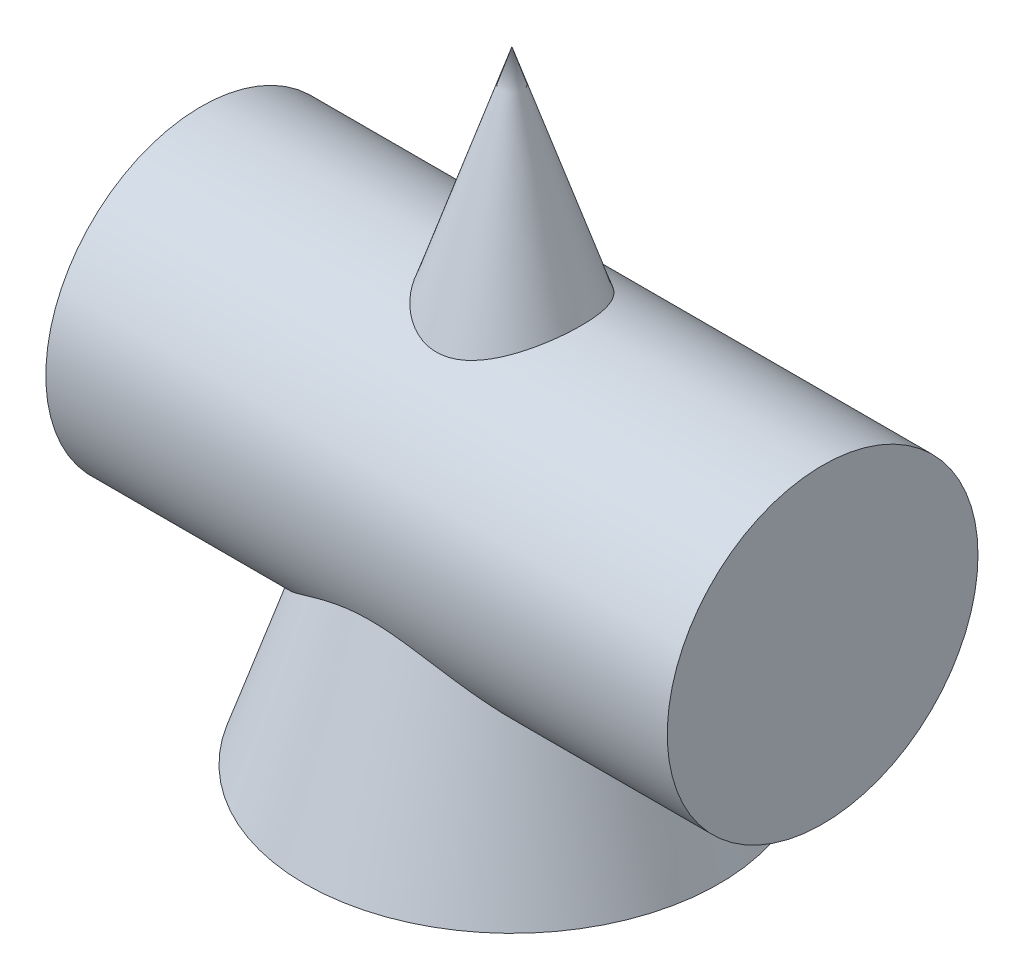
SolidWorks part; units mm, degrees
ref_plane "前视基准面" through (0, 0, 0) normal (0, 0, 1) x (1, 0, 0)
ref_plane "上视基准面" through (0, 0, 0) normal (0, 1, 0) x (1, 0, 0)
ref_plane "右视基准面" through (0, 0, 0) normal (1, 0, 0) x (0, 0, -1)
other "Configuration Table"
sketch "草图1" plane through (0, 0, 0) normal (0, 1, 0) x (1, 0, 0)
  circle A0 centre (0, 0) radius 20
sketch "草图3" plane through (0, 0, 0) normal (0, 0, 1) x (1, 0, 0)
  point P5 (0, 60)
loft "放样2" add profiles "草图1", "草图3"
sketch "草图4" plane through (0, 0, 0) normal (1, 0, 0) x (0, 0, -1)
  circle A1 centre (0, 25) radius 15
extrude "凸台-拉伸2" add sketch "草图4" along normal blind 30 and the other way blind 30
